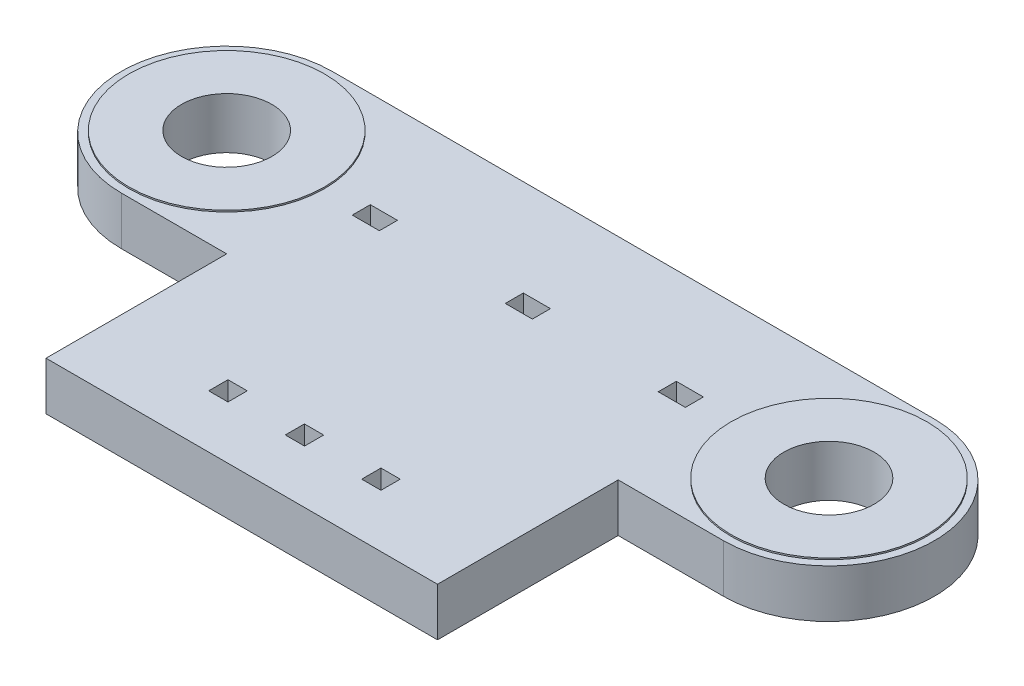
SolidWorks part; units mm, degrees
ref_plane "Front Plane" through (0, 0, 0) normal (0, 0, 1) x (1, 0, 0)
ref_plane "Top Plane" through (0, 0, 0) normal (0, 1, 0) x (1, 0, 0)
ref_plane "Right Plane" through (0, 0, 0) normal (1, 0, 0) x (0, 0, -1)
sketch "Sketch1" plane through (0, 0, 0) normal (0, 1, 0) x (1, 0, 0)
  line L0 (0, 97.8774) -> (0, -75.4137) construction
  line L1 (-187.1972, 0) -> (25.8529, 0) construction
  line L2 (-10, 3.5) -> (10, 3.5)
  line L3 (6.5, -9.5) -> (-6.5, -9.5)
  line L4 (-6.5, -9.5) -> (-6.5, -3.5)
  line L5 (-10, -3.5) -> (-6.5, -3.5)
  line L6 (10, -3.5) -> (6.5, -3.5)
  line L7 (6.5, -9.5) -> (6.5, -3.5)
  arc A0 (-10, 3.5) -> (-10, -3.5) centre (-10, 0) ccw
  circle A1 centre (-10, 0) radius 1.5
  arc A2 (10, 3.5) -> (10, -3.5) centre (10, 0) cw
  circle A3 centre (10, 0) radius 1.5
  point P18 (0, 3.5)
  point P20 (0, -9.5)
  dimension "D1" = 7
  dimension "D3" = 3
  dimension "D2" = 20
  dimension "D4" = 13
  dimension "D5" = 13
extrude "Boss-Extrude1" add sketch "Sketch1" along normal blind 0.8 and the other way blind 0.8
sketch "Sketch4" plane through (0, 0.8, 0) normal (0, 1, 0) x (1, 0, 0)
  line L0 (0, 3.5) -> (0, -9.5) construction
  line L1 (10, 3.5) -> (-10, 3.5) construction
  line L2 (-6.5, -9.5) -> (6.5, -9.5) construction
  circle A4 centre (10, 0) radius 1.5
  circle A5 centre (10, 0) radius 1.5
  circle A6 centre (-10, 0) radius 3.25
  circle A7 centre (-10, 0) radius 1.5
  circle A8 centre (-10, 0) radius 1.5
  circle A9 centre (10, 0) radius 3.25
  dimension "D3" = 6.5
  dimension "D1" = 0
  dimension "D2" = 0
extrude "Boss-Extrude4" add sketch "Sketch4" along normal blind 0.05
mirror "Mirror1" about plane through (0, 0, 0) normal (0, 1, 0) of "Boss-Extrude4"
sketch "Sketch5" plane through (0, 0.8, 0) normal (0, 1, 0) x (1, 0, 0)
  line L0 (0, 3.5) -> (0, -9.5) construction
  line L1 (10, 3.5) -> (-10, 3.5) construction
  line L2 (-6.5, -9.5) -> (6.5, -9.5) construction
  line L3 (-6.5, -7.4175) -> (6.5, -7.4175) construction
  line L4 (-0.32, -7.735) -> (0.32, -7.735)
  line L5 (-0.32, -7.735) -> (-0.32, -7.1)
  line L6 (-0.32, -7.1) -> (0.32, -7.1)
  line L7 (0.32, -7.735) -> (0.32, -7.1)
  line L8 (-0.32, -7.735) -> (0.32, -7.1) construction
  line L9 (-0.32, -7.1) -> (0.32, -7.735) construction
  line L10 (-6.5, -3.5) -> (-6.5, -9.5) construction
  line L11 (6.5, -9.5) -> (6.5, -3.5) construction
  line L12 (-2.22, -7.0975) -> (-2.86, -7.0975)
  line L13 (2.22, -7.7375) -> (2.86, -7.7375)
  line L14 (2.22, -7.7375) -> (2.22, -7.0975)
  line L15 (2.22, -7.0975) -> (2.86, -7.0975)
  line L16 (2.86, -7.7375) -> (2.86, -7.0975)
  line L17 (2.22, -7.7375) -> (2.86, -7.0975) construction
  line L18 (2.22, -7.0975) -> (2.86, -7.7375) construction
  line L19 (-2.86, -7.7375) -> (-2.86, -7.0975)
  line L20 (-2.22, -7.7375) -> (-2.86, -7.7375)
  line L21 (-2.22, -7.7375) -> (-2.22, -7.0975)
  line L22 (-2.22, -7.0975) -> (-2.86, -7.7375) construction
  line L23 (-2.22, -7.7375) -> (-2.86, -7.0975) construction
  point P6 (0, -7.4175)
  point P17 (2.54, -7.4175)
  dimension "D1" = 0.64
  dimension "D2" = 2.4
  dimension "D3" = 2.54
  dimension "D4" = 0.635
extrude "Cut-Extrude1" cut sketch "Sketch5" against normal up to surface (1.6 mm away) up to face at (10, -0.8, -3.25)
sketch "Sketch6" plane through (0, 0.8, 0) normal (0, 1, 0) x (1, 0, 0)
  line L0 (-13.5, 0) -> (13.5, 0) construction
  line L1 (0, 2.9) -> (0, -2.9) construction
  line L2 (-6.4, -2.9) -> (6.4, -2.9) construction
  line L3 (-6.4, -2.9) -> (-6.4, 2.9) construction
  line L4 (-6.4, 2.9) -> (6.4, 2.9) construction
  line L5 (6.4, -2.9) -> (6.4, 2.9) construction
  line L6 (-6.4, -2.9) -> (6.4, 2.9) construction
  line L7 (-6.4, 2.9) -> (6.4, -2.9) construction
  line L8 (-0.45, -0.3) -> (0.45, -0.3)
  line L9 (-0.45, -0.3) -> (-0.45, 0.3)
  line L10 (-0.45, 0.3) -> (0.45, 0.3)
  line L11 (0.45, -0.3) -> (0.45, 0.3)
  line L12 (-0.45, -0.3) -> (0.45, 0.3) construction
  line L13 (-0.45, 0.3) -> (0.45, -0.3) construction
  line L14 (-5.53, -0.3) -> (-4.63, -0.3)
  line L15 (-5.53, -0.3) -> (-5.53, 0.3)
  line L16 (-5.53, 0.3) -> (-4.63, 0.3)
  line L17 (-4.63, -0.3) -> (-4.63, 0.3)
  line L18 (-5.53, -0.3) -> (-4.63, 0.3) construction
  line L19 (-5.53, 0.3) -> (-4.63, -0.3) construction
  line L20 (5.53, -0.3) -> (4.63, 0.3) construction
  line L21 (5.53, 0.3) -> (4.63, -0.3) construction
  line L22 (5.53, 0.3) -> (4.63, 0.3)
  line L23 (4.63, -0.3) -> (4.63, 0.3)
  line L24 (5.53, -0.3) -> (4.63, -0.3)
  line L25 (5.53, -0.3) -> (5.53, 0.3)
  arc A0 (-10, 3.5) -> (-10, -3.5) centre (-10, 0) ccw construction
  arc A1 (10, -3.5) -> (10, 3.5) centre (10, 0) ccw construction
  point P8 (0, 0)
  point P14 (0, 0)
  point P19 (-5.08, 0)
  dimension "D1" = 5.8
  dimension "D2" = 12.8
  dimension "D3" = 0.9
  dimension "D4" = 0.6
  dimension "D5" = 5.08
extrude "Cut-Extrude2" cut sketch "Sketch6" against normal up to surface (1.6 mm away) up to face at (-2.54, -0.8, 7.4175)
